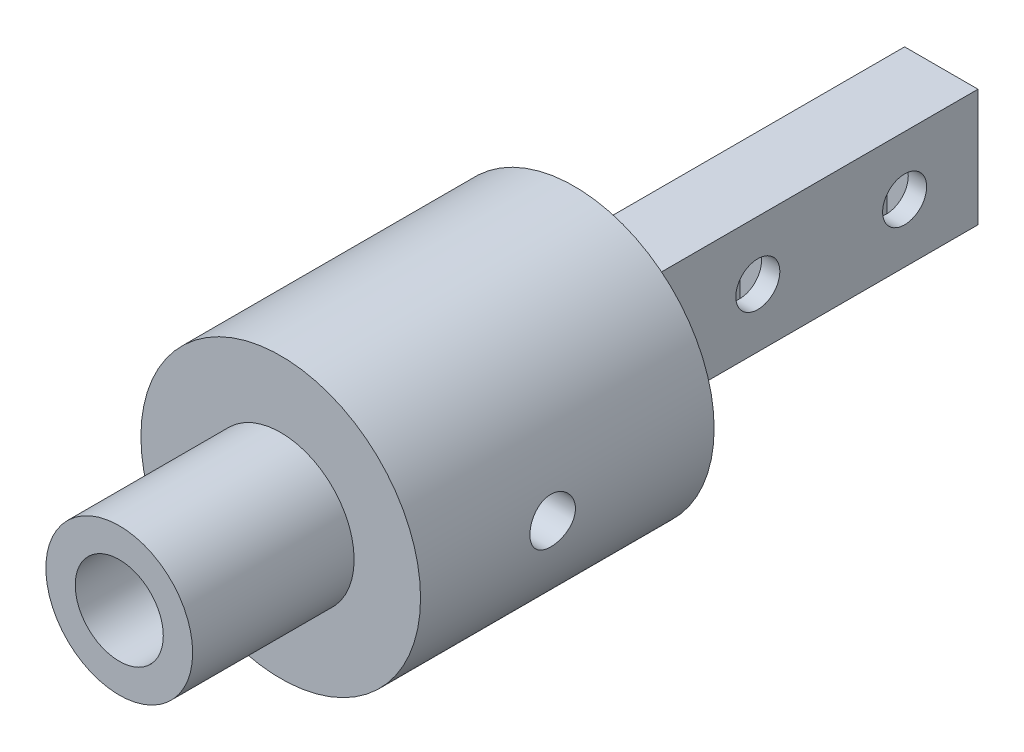
SolidWorks part; units mm, degrees
ref_plane "Front Plane" through (0, 0, 0) normal (0, 0, 1) x (1, 0, 0)
ref_plane "Top Plane" through (0, 0, 0) normal (0, 1, 0) x (1, 0, 0)
ref_plane "Right Plane" through (0, 0, 0) normal (1, 0, 0) x (0, 0, -1)
sketch "Sketch1" plane through (0, 0, 0) normal (0, 1, 0) x (1, 0, 0)
  line L0 (0, 4) -> (-5, 4)
  line L1 (-5, -16) -> (-5, -27)
  line L3 (-3, -27) -> (-3, 0)
  line L4 (-3, 0) -> (0, 0)
  line L5 (0, 0) -> (0, 4)
  line L6 (-5, 4) -> (-9.525, 4)
  line L7 (-9.525, 4) -> (-9.525, -16)
  line L8 (-9.525, -16) -> (-5, -16)
  line L14 (-5, -27) -> (-3, -27)
  point P10 (-1.5, 0)
  dimension "D1" = 20
  dimension "D2" = 11
  dimension "D3" = 2
  dimension "D4" = 5
  dimension "D5" = 4
  dimension "D6" = 9.525
revolve "Revolve1" add sketch "Sketch1" angle 360 about L5
sketch "Sketch2" plane through (0, 0, -4) normal (0, 0, -1) x (-1, 0, 0)
  line L1 (-2.5, 4) -> (2.5, 4)
  line L2 (-2.5, 4) -> (-2.5, -4)
  line L3 (-2.5, -4) -> (2.5, -4)
  line L4 (2.5, 4) -> (2.5, -4)
  line L5 (0, -4) -> (0, 4) construction
  line L6 (-2.5, 0) -> (2.5, 0) construction
  point P0 (0, 0)
  dimension "D1" = 5
  dimension "D2" = 8
extrude "Boss-Extrude1" add sketch "Sketch2" along normal blind 25
sketch "Sketch3" plane through (2.5, 0, 0) normal (1, 0, 0) x (0, 0, -1)
  line L2 (14, -3.1754) -> (16.75, -1.5877) construction
  line L3 (16.75, -1.5877) -> (16.75, 1.5877) construction
  line L4 (16.75, 1.5877) -> (14, 3.1754) construction
  line L5 (14, 3.1754) -> (11.25, 1.5877) construction
  line L6 (11.25, 1.5877) -> (11.25, -1.5877) construction
  line L7 (11.25, -1.5877) -> (14, -3.1754) construction
  line L8 (4, 4) -> (4, -4) construction
  circle A0 centre (14, 0) radius 2.75 construction
  point P0 (24, 0)
  point P1 (14, 0)
  dimension "D1" = 10
  dimension "D2" = 10
  dimension "D3" = 5.5
hole_wizard "M2.5 Clearance Hole1" positions "Sketch3" profile "Sketch4" hole size "M2.5" standard "ANSI Metric"
sketch "Sketch4" plane through (2.5, 0, -24) normal (0, 1, 0) x (0, 0, -1)
  line L0 (0, 0) -> (0, 10)
  line L1 (0, 10) -> (1.5, 9.0987)
  line L2 (1.5, 9.0987) -> (1.5, 0)
  line L5 (1.5, 0) -> (0, 0)
  line L10 (0, 10) -> (-1.5, 9.0987) construction
  line L11 (0, -6.35) -> (0, 107.95) construction
  dimension "Hole Dia." = 3
  dimension "Hole Depth" = 10
  dimension "Drill Angle" = 118
sketch "Sketch5" plane through (0, -4, 0) normal (0, -1, 0) x (1, 0, 0)
  line L1 (-1.25, -11.45) -> (1.25, -11.45)
  line L2 (-1.25, -11.45) -> (-1.25, -16.55)
  line L3 (-1.25, -16.55) -> (1.25, -16.55)
  line L4 (1.25, -11.45) -> (1.25, -16.55)
  line L5 (0, -16.55) -> (0, -11.45) construction
  line L6 (-1.25, -14) -> (1.25, -14) construction
  line L7 (-1.25, -21.45) -> (1.25, -21.45)
  line L8 (-1.25, -21.45) -> (-1.25, -26.55)
  line L9 (-1.25, -26.55) -> (1.25, -26.55)
  line L10 (1.25, -21.45) -> (1.25, -26.55)
  line L11 (0, -26.55) -> (0, -21.45) construction
  line L12 (-1.25, -24) -> (1.25, -24) construction
  line L13 (2.5, -29) -> (2.5, -4) construction
  point P0 (0, -14)
  point P4 (0, -24)
  dimension "D1" = 5.1
  dimension "D2" = 2.5
  dimension "D3" = 2.5
extrude "Cut-Extrude1" cut sketch "Sketch5" against normal offset from surface (7.2 mm away) 0.8 up to face at (0, 4, -16.5)
sketch "Sketch6" plane through (-2.5, 0, 0) normal (-1, 0, 0) x (0, 0, 1)
  line L1 (-11.45, -1.4722) -> (-11.45, 1.4722)
  line L2 (-11.45, 1.4722) -> (-14, 2.9445)
  line L3 (-14, 2.9445) -> (-16.55, 1.4722)
  line L4 (-16.55, 1.4722) -> (-16.55, -1.4722)
  line L5 (-16.55, -1.4722) -> (-14, -2.9445)
  line L6 (-14, -2.9445) -> (-11.45, -1.4722)
  line L7 (-24, -2.9445) -> (-21.45, -1.4722)
  line L8 (-21.45, -1.4722) -> (-21.45, 1.4722)
  line L9 (-21.45, 1.4722) -> (-24, 2.9445)
  line L10 (-24, 2.9445) -> (-26.55, 1.4722)
  line L11 (-26.55, 1.4722) -> (-26.55, -1.4722)
  line L12 (-26.55, -1.4722) -> (-24, -2.9445)
  circle A0 centre (-14, 0) radius 2.55 construction
  circle A1 centre (-24, 0) radius 2.55 construction
  dimension "D1" = 5.1
  dimension "D2" = 5.1
ref_plane "Plane1" through (-9.525, 0, 0) normal (-1, 0, 0) x (0, 0, 1)
sketch "Sketch7" plane through (-9.525, 0, 0) normal (-1, 0, 0) x (0, 0, 1)
  line L0 (27, -5) -> (27, 5) construction
  line L2 (7, -2.9445) -> (9.55, -1.4722)
  line L3 (9.55, -1.4722) -> (9.55, 1.4722)
  line L4 (9.55, 1.4722) -> (7, 2.9445)
  line L5 (7, 2.9445) -> (4.45, 1.4722)
  line L6 (4.45, 1.4722) -> (4.45, -1.4722)
  line L7 (4.45, -1.4722) -> (7, -2.9445)
  circle A0 centre (7, 0) radius 0.5
  circle A1 centre (7, 0) radius 2.55 construction
  point P0 (7, 0)
  dimension "D1" = 1
  dimension "D2" = 20
  dimension "D3" = 5.1
hole_wizard "M2.5 Clearance Hole2" positions "Sketch7" profile "Sketch9" hole size "M2.5" standard "ISO" end condition through all
sketch "Sketch9" plane through (-9.525, 0, 7) normal (0, 1, 0) x (0, 0, 1)
  line L0 (0, 0) -> (0, 19.05)
  line L1 (0, 19.05) -> (1.55, 19.05)
  line L2 (1.55, 19.05) -> (1.55, 0)
  line L5 (1.55, 0) -> (0, 0)
  line L11 (0, -6.35) -> (0, 107.95) construction
  dimension "Thru Hole Dia." = 3.1
  dimension "Thru Hole Depth" = 19.05
extrude "Cut-Extrude2" cut sketch "Sketch7<2>" against normal blind 2.5
sketch "Sketch7<2>" plane through (-9.525, 0, 0) normal (-1, 0, 0) x (0, 0, 1) same geometry as "Sketch7"
